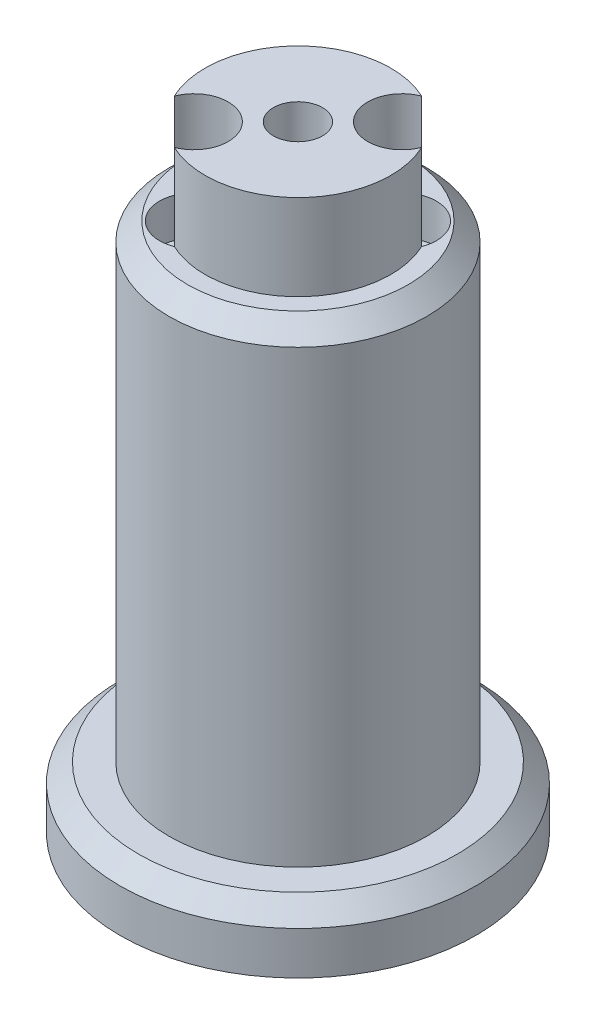
SolidWorks part; units mm, degrees
material "3DP Resin"
ref_plane "Front Plane" through (0, 0, 0) normal (0, 0, 1) x (1, 0, 0)
ref_plane "Top Plane" through (0, 0, 0) normal (0, 1, 0) x (1, 0, 0)
ref_plane "Right Plane" through (0, 0, 0) normal (1, 0, 0) x (0, 0, -1)
sketch "Sketch1" plane through (0, 0, 0) normal (0, 1, 0) x (1, 0, 0)
  circle A0 centre (0, 0) radius 14.5
  dimension "D1" = 29
extrude "Boss-Extrude1" add sketch "Sketch1" along normal blind 5
sketch "Sketch2" plane through (0, 0, 0) normal (0, -1, 0) x (1, 0, 0)
  circle A0 centre (0, 0) radius 13
  dimension "D1" = 26
extrude "Cut-Extrude1" cut sketch "Sketch2" against normal blind 3
sketch "Sketch6" plane through (0, 5, 0) normal (0, 1, 0) x (1, 0, 0)
  circle A0 centre (0, 0) radius 10.5
  dimension "D1" = 21
extrude "Boss-Extrude3" add sketch "Sketch6" along normal blind 45.2
sketch "Sketch3" plane through (0, 5, 0) normal (0, 1, 0) x (1, 0, 0)
  line L0 (14.5, 0) -> (-14.5, 0) construction
  line L1 (0, -14.5) -> (0, 14.5) construction
  line L2 (-4.2426, 4.2426) -> (0, 0) construction
  circle A0 centre (0, 0) radius 3
  circle A1 centre (0, 0) radius 14.5 construction
  circle A2 centre (0, 0) radius 6 construction
  circle A3 centre (-4.2426, 4.2426) radius 1.5
  circle A5 centre (4.2426, 4.2426) radius 1.5
  circle A6 centre (4.2426, -4.2426) radius 1.5
  circle A7 centre (-4.2426, -4.2426) radius 1.5
  point P7 (0, 0)
  point P11 (0, 0)
  point P23 (0, 0)
  dimension "D1" = 6
  dimension "D2" = 12
  dimension "D3" = 3
  dimension "D4" = 45
  dimension "D5" = 4
extrude "Cut-Extrude2" cut sketch "Sketch3" along normal blind 5 from surface starting at face at (0, 3, -13)
sketch "Sketch7" plane through (0, 50.2, 0) normal (0, 1, 0) x (1, 0, 0)
  circle A0 centre (0, 0) radius 10.5
  circle A1 centre (0, 0) radius 7.575
  dimension "D1" = 15.15
  dimension "D2" = 21
extrude "Bearing Support" cut sketch "Sketch7" against normal blind 7
sketch "Sketch8" plane through (0, 3, 0) normal (0, -1, 0) x (1, 0, 0)
  line L0 (-13, 0) -> (13, 0) construction
  line L1 (0, -13) -> (0, 13) construction
  line L2 (-4.2426, 4.2426) -> (0, 0) construction
  line L3 (0, 0) -> (4.2426, -4.2426) construction
  circle A0 centre (0, 0) radius 2
  circle A1 centre (0, 0) radius 13 construction
  circle A2 centre (0, 0) radius 13 construction
  circle A3 centre (-4.2426, 4.2426) radius 1.5
  circle A4 centre (0, 0) radius 6 construction
  circle A5 centre (4.2426, -4.2426) radius 1.5
  circle A6 centre (-4.2426, 4.2426) radius 1.5 construction
  point P6 (0, 0)
  point P31 (0, 0)
  dimension "D1" = 4
  dimension "D2" = 3
  dimension "D3" = 12
  dimension "D4" = 45
extrude "M4 Hole Bore" cut sketch "Sketch8" against normal through all
sketch "Sketch9" plane through (0, 50.2, 0) normal (0, 1, 0) x (1, 0, 0)
  circle A0 centre (4.2426, 4.2426) radius 1.5 construction
  circle A1 centre (-4.2426, -4.2426) radius 1.5 construction
  circle A2 centre (4.2426, 4.2426) radius 1.5 construction
  circle A3 centre (-4.2426, -4.2426) radius 1.5 construction
  circle A4 centre (4.2426, 4.2426) radius 2.8
  circle A5 centre (-4.2426, -4.2426) radius 2.8
  dimension "D1" = 5.6
extrude "M3 Bolt Recesses" cut sketch "Sketch9" against normal blind 10.2
chamfer "Chamfer1" distance 1.5 angle 45 2 edges at (0, 43.2, 10.5) (0, 5, 14.5)
